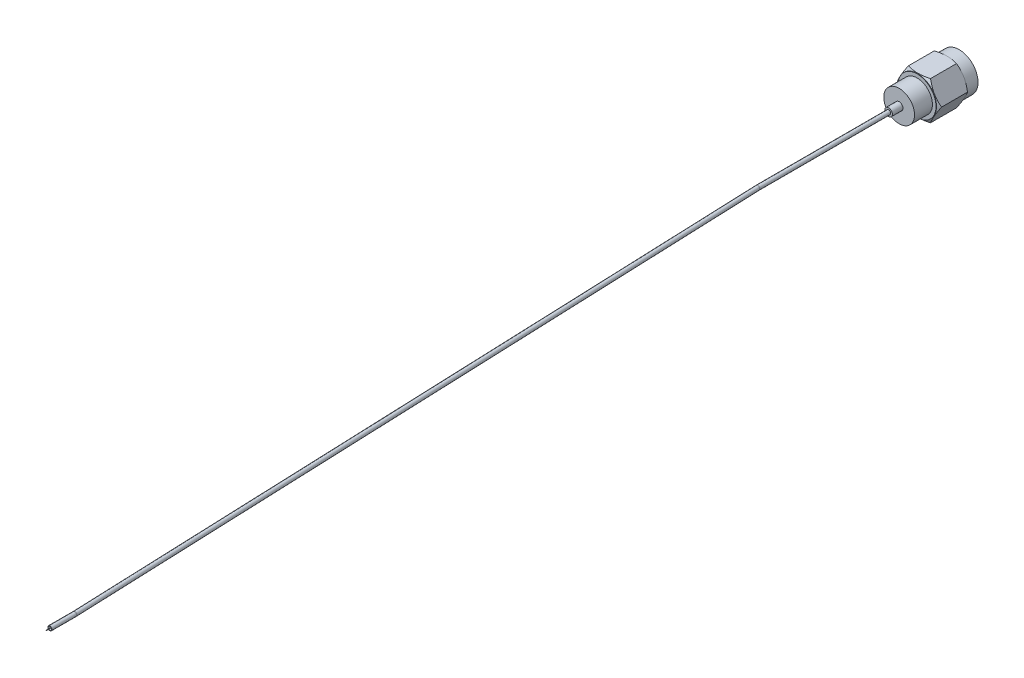
SolidWorks part; units mm, degrees
ref_plane "Front Plane" through (0, 0, 0) normal (0, 0, 1) x (1, 0, 0)
ref_plane "Top Plane" through (0, 0, 0) normal (0, 1, 0) x (1, 0, 0)
ref_plane "Right Plane" through (0, 0, 0) normal (1, 0, 0) x (0, 0, -1)
ref_axis "Axis1" through (0, 0, -0.4923) along (0, 0, 1)
sketch "Sketch1" plane through (0, 0, 0) normal (0, 0, 1) x (1, 0, 0)
  circle A0 centre (-0.635, 0) radius 0.4318
  circle A1 centre (-0.635, 0) radius 0.3429
  dimension "D1" = 0.6858
  dimension "D2" = 0.8636
  dimension "D3" = 0.635
sketch "Sketch2" plane through (0, 0, 0) normal (0, 1, 0) x (1, 0, 0)
  line L0 (-0.635, 0) -> (-0.635, 5.08)
  line L1 (-0.6369, 5.1787) -> (-6.3481, 151.9936)
  line L2 (-6.35, 152.0923) -> (-6.35, 181.2798)
  arc A0 (-6.3481, 151.9936) -> (-6.35, 152.0923) centre (-3.81, 152.0923) cw
  arc A1 (-0.635, 5.08) -> (-0.6369, 5.1787) centre (-3.175, 5.08) ccw
  point P9 (-6.35, 193.675)
  point P11 (-6.35, 172.3136)
  point P12 (-6.35, 173.1264)
  dimension "D1" = 2.54
  dimension "D2" = 5.08
  dimension "D3" = 6.35
  dimension "D4" = 0.8128
  dimension "D5" = 2.228
  dimension "D7" = 193.675
  dimension "D8" = 12.3952
  dimension "D9" = 172.3136
  dimension "D10" = 20.32
sweep "SW-00 Jacket & Layout" add profiles "Sketch1" path "Sketch2"
sketch "Sketch3" plane through (0, 0, 0) normal (0, 1, 0) x (1, 0, 0)
  line L0 (-6.35, 179.0954) -> (-5.5626, 179.0954)
  line L1 (-5.5626, 179.0954) -> (-5.5626, 181.2798)
  line L2 (-5.5626, 181.2798) -> (-3.175, 181.2798)
  line L3 (-3.175, 181.2798) -> (-3.175, 184.9882)
  line L4 (-3.175, 184.9882) -> (-2.4384, 184.9882)
  line L5 (-2.4384, 185.0898) -> (-1.4224, 185.6764)
  line L6 (-1.4224, 185.6764) -> (-1.4224, 190.65)
  line L7 (-1.4224, 190.65) -> (-2.4384, 191.2366)
  line L8 (-2.4384, 193.675) -> (-3.81, 193.675)
  line L9 (-3.81, 193.675) -> (-3.81, 187.325)
  line L10 (-3.81, 187.325) -> (-6.35, 187.325)
  line L11 (-6.35, 187.325) -> (-6.35, 179.0954)
  line L12 (-6.35, 187.325) -> (-6.35, 18.976) construction
  line L13 (-2.4384, 184.9882) -> (-2.4384, 185.0898)
  line L14 (-2.4384, 193.675) -> (-2.4384, 191.2366)
  dimension "D1" = 1.5748
  dimension "D2" = 30
  dimension "D3" = 30
  dimension "D4" = 0.1016
  dimension "D5" = 12.3952
  dimension "D6" = 8.5852
  dimension "D7" = 1.016
  dimension "D9" = 6.35
  dimension "D10" = 5.08
  dimension "D11" = 2.1844
  dimension "D12" = 6.35
  dimension "D13" = 7.8232
  dimension "D14" = 2.4384
  dimension "D15" = 3.7084
revolve "BR-00 Connector Body" add sketch "Sketch3" angle 360 about L12
sketch "Sketch4" plane through (0, 0, -193.675) normal (0, 0, -1) x (-1, 0, 0)
  line L7 (10.9254, 0) -> (8.6377, 3.9624)
  line L8 (8.6377, 3.9624) -> (4.0623, 3.9624)
  line L9 (4.0623, 3.9624) -> (1.7746, 0)
  line L10 (1.7746, 0) -> (4.0623, -3.9624)
  line L11 (4.0623, -3.9624) -> (8.6377, -3.9624)
  line L12 (8.6377, -3.9624) -> (10.9254, 0)
  circle A0 centre (6.35, 0) radius 5.2932
  circle A1 centre (6.35, 0) radius 3.9624 construction
  dimension "D1" = 7.9248
extrude "CE-00 Connector Hex Cut" cut sketch "Sketch4" against normal up to surface (8.6868 mm away) up to face at (-10.2616, 0, -184.9882)
sketch "Sketch5" plane through (0, 0, 0) normal (0, 0, 1) x (1, 0, 0)
  circle A0 centre (-0.635, 0) radius 0.0356
  dimension "D1" = 0.0711
extrude "BE-00 Pin LNA End" add sketch "Sketch5" along normal blind 0.762 and the other way blind 2.54 separate body
sketch "Sketch6" plane through (0, 0, 0) normal (0, 1, 0) x (1, 0, 0)
  line L0 (-6.35, 206.248) -> (-6.35, 173.1264)
  line L1 (-6.35, 173.1264) -> (-6.096, 173.1264)
  line L2 (-6.096, 173.1264) -> (-6.096, 172.3136)
  line L3 (-6.096, 172.3136) -> (0, 172.3136)
  line L4 (0, 172.3136) -> (0, 206.248)
  line L5 (0, 206.248) -> (-6.35, 206.248)
  line L6 (-6.35, 206.248) -> (-6.35, 214.5841) construction
  dimension "D2" = 12.7
  dimension "D3" = 0.508
revolve "CR-00 Strip Jacket" [suppressed] cut sketch "Sketch6" angle 360 about L6
sketch "Sketch8" plane through (0, 0, 0) normal (0, 1, 0) x (1, 0, 0)
  line L0 (-6.35, 173.1264) -> (-6.35, 171.2722)
  line L1 (-6.35, 171.2722) -> (-5.9817, 171.2722)
  line L2 (-5.9817, 171.2722) -> (-5.9817, 172.2882)
  line L3 (-5.9817, 172.2882) -> (-6.3144, 172.2882)
  line L4 (-6.3144, 172.2882) -> (-6.3144, 173.1264)
  line L5 (-6.3144, 173.1264) -> (-6.35, 173.1264)
  line L6 (-6.35, 173.1264) -> (-6.35, 182.4944) construction
  line L7 (-6.096, 172.3136) -> (0, 172.3136) construction
  dimension "D1" = 0.0254
  dimension "D3" = 1.016
  dimension "D4" = 0.0711
  dimension "D5" = 0.7366
revolve "BR-00 Pin Tip End" [suppressed] add sketch "Sketch8" angle 360 about L6
mirror "Mirror3" [suppressed] about plane through (0, 0, 0) normal (1, 0, 0) of bodies 129 131
